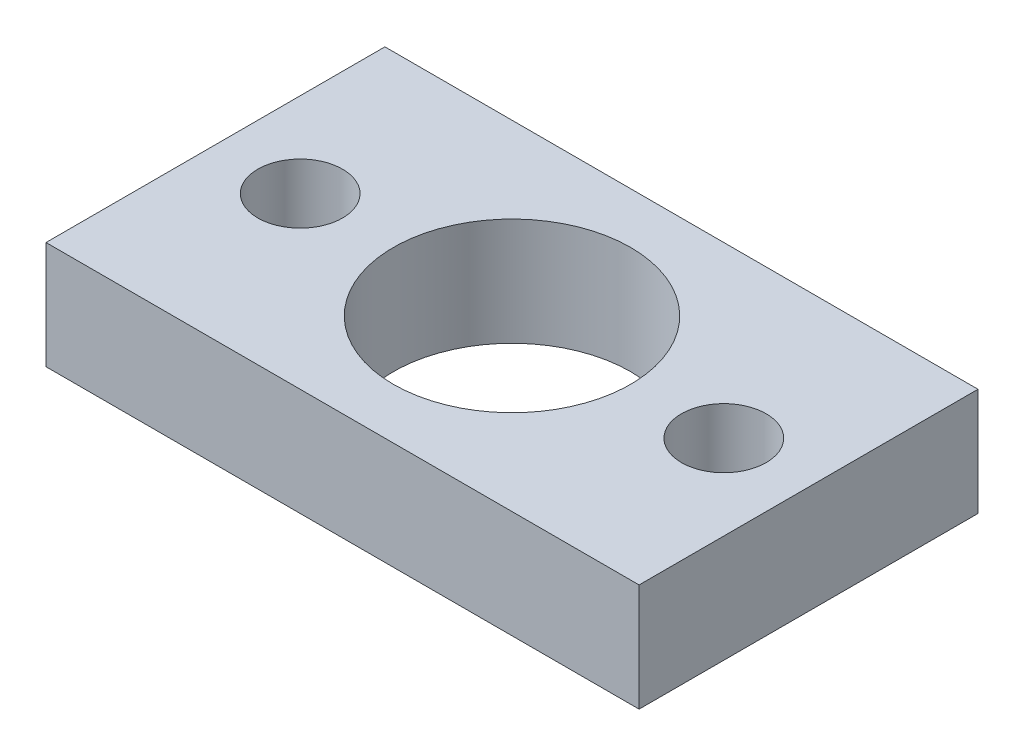
SolidWorks part; units mm, degrees
ref_plane "Front Plane" through (0, 0, 0) normal (0, 0, 1) x (1, 0, 0)
ref_plane "Top Plane" through (0, 0, 0) normal (0, 1, 0) x (1, 0, 0)
ref_plane "Right Plane" through (0, 0, 0) normal (1, 0, 0) x (0, 0, -1)
sketch "Sketch1" plane through (0, 0, 0) normal (0, 1, 0) x (1, 0, 0)
  line L0 (-12.5, 0) -> (12.5, 0) construction
  line L2 (-17.5, -10) -> (17.5, -10)
  line L3 (-17.5, -10) -> (-17.5, 10)
  line L4 (-17.5, 10) -> (17.5, 10)
  line L5 (17.5, -10) -> (17.5, 10)
  line L6 (-17.5, -10) -> (17.5, 10) construction
  line L7 (-17.5, 10) -> (17.5, -10) construction
  circle A0 centre (0, 0) radius 7
  circle A1 centre (12.5, 0) radius 2.5
  circle A2 centre (-12.5, 0) radius 2.5
  dimension "D1" = 14
  dimension "D2" = 5
  dimension "D3" = 25
  dimension "D4" = 35
  dimension "D5" = 20
extrude "Boss-Extrude1" add sketch "Sketch1" along normal mid plane 6.35
